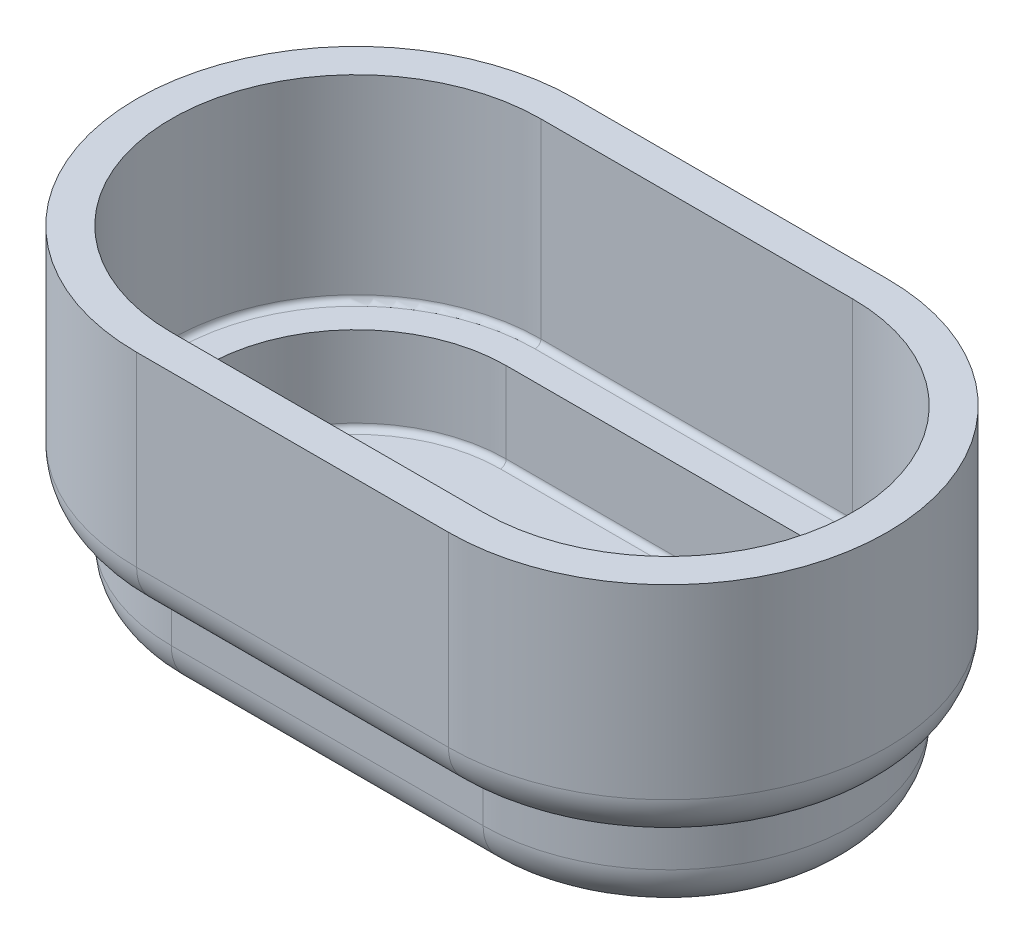
SolidWorks part; units mm, degrees
ref_plane "정면" through (0, 0, 0) normal (0, 0, 1) x (1, 0, 0)
ref_plane "윗면" through (0, 0, 0) normal (0, 1, 0) x (1, 0, 0)
ref_plane "우측면" through (0, 0, 0) normal (1, 0, 0) x (0, 0, -1)
sketch "스케치1" plane through (0, 0, 0) normal (0, 1, 0) x (1, 0, 0)
  line L0 (-23.3429, 0) -> (30.6571, 0) construction
  line L1 (-23.3429, 38) -> (30.6571, 38)
  line L2 (-23.3429, -38) -> (30.6571, -38)
  line L3 (-23.3429, 0) -> (30.6571, 0) construction
  line L4 (-23.3429, 32) -> (30.6571, 32)
  line L5 (-23.3429, -32) -> (30.6571, -32)
  arc A0 (-23.3429, 38) -> (-23.3429, -38) centre (-23.3429, 0) ccw
  arc A1 (30.6571, -38) -> (30.6571, 38) centre (30.6571, 0) ccw
  arc A2 (-23.3429, 32) -> (-23.3429, -32) centre (-23.3429, 0) ccw
  arc A3 (30.6571, -32) -> (30.6571, 32) centre (30.6571, 0) ccw
  point P3 (3.6571, 0)
  point P10 (3.6571, 0)
  dimension "D2" = 38
  dimension "D3" = 32
  dimension "D1" = 54
extrude "보스-돌출1" add sketch "스케치1" against normal blind 40 contours L1 A1 L2 A0
extrude "보스-돌출2" add sketch "스케치1<3>" against normal blind 55 contours A2 L5 A3 L4
sketch "스케치1<3>" plane through (0, 0, 0) normal (0, 1, 0) x (1, 0, 0) same geometry as "스케치1"
shell "쉘1" thickness 6 removed face at (3.6571, 0, 0)
fillet "필렛1" radius 8 8 edges at (3.6571, -40, 38) (-61.3429, -40, 0) (3.6571, -40, -38) (3.6571, -55, 32) (-55.3429, -55, 0) (3.6571, -55, -32) (68.6571, -40, 0) (62.6571, -55, 0)
fillet "필렛3" radius 1 8 edges at (-49.3429, -49, 0) (3.6571, -49, 26) (56.6571, -49, 0) (-55.3429, -34, 0) (3.6571, -34, 32) (62.6571, -34, 0) (3.6571, -49, -26) (3.6571, -34, -32)
